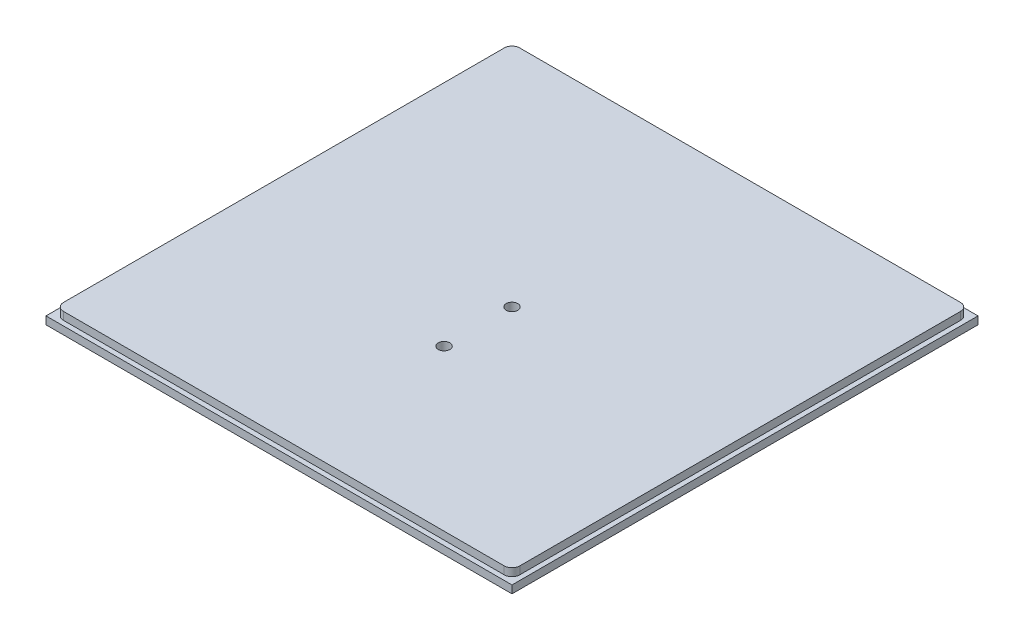
SolidWorks part; units mm, degrees
ref_plane "Front Plane" through (0, 0, 0) normal (0, 0, 1) x (1, 0, 0)
ref_plane "Top Plane" through (0, 0, 0) normal (0, 1, 0) x (1, 0, 0)
ref_plane "Right Plane" through (0, 0, 0) normal (1, 0, 0) x (0, 0, -1)
sketch "Sketch1" plane through (0, 0, 0) normal (0, 1, 0) x (1, 0, 0)
  line L1 (-60, -60) -> (60, -60)
  line L2 (-60, -60) -> (-60, 60)
  line L3 (-60, 60) -> (60, 60)
  line L4 (60, -60) -> (60, 60)
  line L5 (-60, -60) -> (60, 60) construction
  line L6 (-60, 60) -> (60, -60) construction
  point P0 (0, 0)
  dimension "D1" = 120
  dimension "D2" = 120
extrude "Boss-Extrude1" add sketch "Sketch1" along normal blind 2
sketch "Sketch2" plane through (0, 2, 0) normal (0, 1, 0) x (1, 0, 0)
  line L1 (-58.75, -58.75) -> (58.75, -58.75)
  line L2 (-58.75, -58.75) -> (-58.75, 58.75)
  line L3 (-58.75, 58.75) -> (58.75, 58.75)
  line L4 (58.75, -58.75) -> (58.75, 58.75)
  line L5 (-58.75, -58.75) -> (58.75, 58.75) construction
  line L6 (-58.75, 58.75) -> (58.75, -58.75) construction
  point P0 (0, 0)
  dimension "D1" = 117.5
  dimension "D2" = 117.5
extrude "Boss-Extrude2" add sketch "Sketch2" along normal blind 2
fillet "Fillet1" radius 2 4 edges at (-58.75, 3, -58.75) (58.75, 3, -58.75) (58.75, 3, 58.75) (-58.75, 3, 58.75)
sketch "Sketch4" plane through (0, 0, 0) normal (0, -1, 0) x (1, 0, 0)
  circle A0 centre (0, 0) radius 1.5
  circle A1 centre (0, 17.5) radius 1.5
  dimension "D1" = 3
  dimension "D2" = 3
  dimension "D3" = 17.5
extrude "Cut-Extrude1" cut sketch "Sketch4" against normal through all
